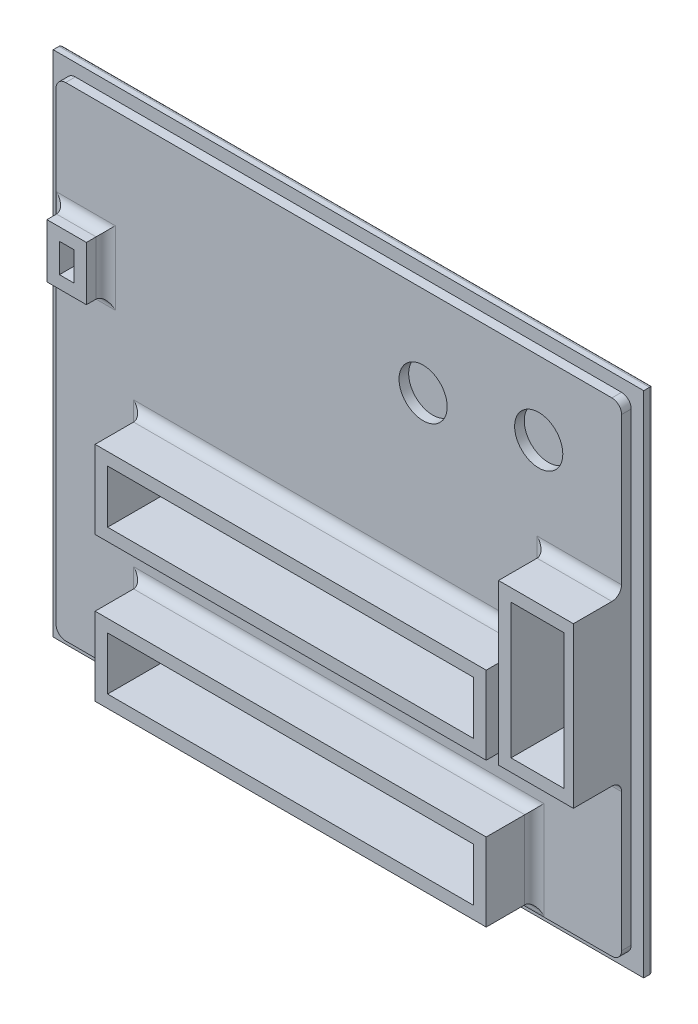
SolidWorks part; units mm, degrees
ref_plane "Płaszczyzna przednia" through (0, 0, 0) normal (0, 0, 1) x (1, 0, 0)
ref_plane "Płaszczyzna górna" through (0, 0, 0) normal (0, 1, 0) x (1, 0, 0)
ref_plane "Płaszczyzna prawa" through (0, 0, 0) normal (1, 0, 0) x (0, 0, -1)
sketch "Outside dim" plane through (0, 0, 0) normal (0, 0, 1) x (1, 0, 0)
  line L1 (-30.65, 26.4) -> (30.65, 26.4)
  line L2 (-30.65, 26.4) -> (-30.65, -26.4)
  line L3 (-30.65, -26.4) -> (30.65, -26.4)
  line L4 (30.65, 26.4) -> (30.65, -26.4)
  point P4 (0, 26.4)
  point P6 (-30.65, 0)
  dimension "D1" = 61.3
  dimension "D2" = 52.8
sketch "Inside dim" plane through (0, 0, 0) normal (0, 0, 1) x (1, 0, 0)
  line L1 (-29.35, 25.1) -> (29.35, 25.1)
  line L2 (-29.35, 25.1) -> (-29.35, -25.1)
  line L3 (-29.35, -25.1) -> (29.35, -25.1)
  line L4 (29.35, 25.1) -> (29.35, -25.1)
  point P4 (0, 25.1)
  point P6 (-29.35, 0)
  dimension "D1" = 58.7
  dimension "D2" = 50.2
extrude "Dodanie-wyciągnięcie1" add sketch "Outside dim" against normal blind 1
extrude "Dodanie-wyciągnięcie2" add sketch "Inside dim" along normal blind 1
sketch "PCB dim" plane through (0, 0, 1) normal (0, 0, 1) x (1, 0, 0)
  line L1 (-28.75, 24.5) -> (28.75, 24.5)
  line L2 (-28.75, 24.5) -> (-28.75, -24.5)
  line L3 (-28.75, -24.5) -> (28.75, -24.5)
  line L4 (28.75, 24.5) -> (28.75, -24.5)
  point P4 (0, 24.5)
  point P6 (-28.75, 0)
  dimension "D1" = 57.5
  dimension "D2" = 49
sketch "Capacitors" plane through (0, 0, 1) normal (0, 0, 1) x (1, 0, 0)
  circle A0 centre (8.75, 15.75) radius 2.5
  circle A1 centre (20.75, 17.5) radius 2.5
  dimension "D1" = 5
  dimension "D2" = 5
  dimension "D3" = 8
  dimension "D4" = 7
  dimension "D5" = 8.75
  dimension "D6" = 20
extrude "Capacitors cutout" cut sketch "Capacitors" against normal up to surface (1 mm away) up to face at (0, 0, 0)
sketch "Reset button" plane through (0, 0, 1) normal (0, 0, 1) x (1, 0, 0)
  line L0 (-28.75, 24.5) -> (-28.75, -24.5) construction
  line L1 (-24.2, 13.8) -> (-28.3, 13.8)
  line L2 (-24.2, 13.8) -> (-24.2, 8.2)
  line L3 (-24.2, 8.2) -> (-28.3, 8.2)
  line L4 (-28.3, 13.8) -> (-28.3, 8.2)
  line L5 (-25.5, 12.5) -> (-27, 12.5)
  line L6 (-25.5, 12.5) -> (-25.5, 9.5)
  line L7 (-25.5, 9.5) -> (-27, 9.5)
  line L8 (-27, 12.5) -> (-27, 9.5)
  line L9 (-28.75, 24.5) -> (28.75, 24.5) construction
  point P8 (-26.25, 13.8)
  point P11 (-27, 11)
  dimension "D1" = 1.3
  dimension "D2" = 1.3
  dimension "D3" = 1.3
  dimension "D4" = 1.3
  dimension "D5" = 2.5
  dimension "D6" = 13.5
  dimension "D7" = 1.5
  dimension "D8" = 3
extrude "Reset button shield" add sketch "Reset button" along normal blind 2 contours L4 L3 L2 L1
extrude "Reset button cutout" cut sketch "Szkic5<3>" against normal through all both and the other way through all contours L5 L8 L7 L6
sketch "Szkic5<3>" plane through (0, 0, 1) normal (0, 0, 1) x (1, 0, 0) same geometry as "Reset button"
sketch "SWDIO" plane through (0, 0, 1) normal (0, 0, 1) x (1, 0, 0)
  line L0 (28.75, 24.5) -> (28.75, -24.5) construction
  line L1 (22.875, 6.5) -> (28.375, 6.5)
  line L2 (22.875, 6.5) -> (22.875, -7.5)
  line L3 (22.875, -7.5) -> (28.375, -7.5)
  line L4 (28.375, 6.5) -> (28.375, -7.5)
  line L5 (21.575, 7.8) -> (29.35, 7.8)
  line L6 (21.575, 7.8) -> (21.575, -8.8)
  line L7 (21.575, -8.8) -> (29.35, -8.8)
  line L8 (29.35, 7.8) -> (29.35, -8.8)
  line L9 (29.35, -25.1) -> (29.35, 25.1) construction
  point P10 (25.625, -7.5)
  point P11 (22.875, -0.5)
  dimension "D1" = 5.5
  dimension "D2" = 14
  dimension "D3" = 1.3
  dimension "D4" = 1.3
  dimension "D5" = 1.3
  dimension "D7" = 3.125
  dimension "D8" = 25
extrude "SWDIO shield" add sketch "SWDIO" along normal blind 5 contours L5 L8 L7 L6
extrude "SWDIO cutout" cut sketch "Szkic6<3>" against normal through all both and the other way through all contours L1 L4 L3 L2
sketch "Szkic6<3>" plane through (0, 0, 1) normal (0, 0, 1) x (1, 0, 0) same geometry as "SWDIO"
sketch "Art skin connectors" plane through (0, 0, 1) normal (0, 0, 1) x (1, 0, 0)
  line L0 (-28.75, -24.5) -> (28.75, -24.5) construction
  line L1 (-19, -2.2) -> (19, -2.2)
  line L2 (-19, -2.2) -> (-19, -7.7)
  line L3 (-19, -7.7) -> (19, -7.7)
  line L4 (19, -2.2) -> (19, -7.7)
  line L5 (-19, -17.2) -> (19, -17.2)
  line L6 (-19, -17.2) -> (-19, -22.7)
  line L7 (-19, -22.7) -> (19, -22.7)
  line L8 (19, -17.2) -> (19, -22.7)
  line L9 (-20.3, -15.9) -> (20.3, -15.9)
  line L10 (-20.3, -15.9) -> (-20.3, -24)
  line L11 (-20.3, -24) -> (20.3, -24)
  line L12 (20.3, -15.9) -> (20.3, -24)
  line L13 (-20.3, -0.9) -> (20.3, -0.9)
  line L14 (-20.3, -0.9) -> (-20.3, -9)
  line L15 (-20.3, -9) -> (20.3, -9)
  line L16 (20.3, -0.9) -> (20.3, -9)
  point P16 (0, -2.2)
  point P17 (0, -17.2)
  point P20 (0, -24.5)
  point P21 (-19, -19.95)
  point P23 (-19, -4.95)
  dimension "D1" = 38
  dimension "D2" = 1.3
  dimension "D3" = 1.3
  dimension "D4" = 1.3
  dimension "D5" = 1.3
  dimension "D6" = 1.3
  dimension "D7" = 1.3
  dimension "D8" = 5.5
  dimension "D9" = 5.5
  dimension "D10" = 1.3
  dimension "D11" = 1.3
  dimension "D12" = 4.55
  dimension "D13" = 19.55
extrude "Art skin connectors shield" add sketch "Art skin connectors" along normal up to surface (5 mm away) up to face at (25.625, -0.5, 6)
extrude "Art skin connectors cutout" cut sketch "Szkic7<2>" against normal through all both and the other way through all contours L8 L7 L6 L5 | L1 L4 L3 L2
sketch "Szkic7<2>" plane through (0, 0, 1) normal (0, 0, 1) x (1, 0, 0) same geometry as "Art skin connectors"
fillet "Bottom of print curve" radius 0.4 20 edges at (19, -19.95, -1) (0, -22.7, -1) (-19, -19.95, -1) (0, -17.2, -1) (19, -4.95, -1) (0, -7.7, -1) (-19, -4.95, -1) (0, -2.2, -1) (28.375, -0.5, -1) (25.625, -7.5, -1) (22.875, -0.5, -1) (25.625, 6.5, -1) (0, -26.4, -1) (30.65, 0, -1) (0, 26.4, -1) (-30.65, 0, -1) (-26.25, 9.5, -1) (-27, 11, -1) (-26.25, 12.5, -1) (-25.5, 11, -1)
fillet "Side mount surve" radius 1 4 edges at (29.35, -25.1, 0.5) (-29.35, -25.1, 0.5) (29.35, 25.1, 0.5) (-29.35, 25.1, 0.5)
fillet "Curve all shields" radius 1 15 edges at (0, -24, 1) (-28.3, 11, 1) (25.4625, 7.8, 1) (-26.25, 13.8, 1) (-24.2, 11, 1) (-26.25, 8.2, 1) (0, -0.9, 1) (-20.3, -4.95, 1) (0, -15.9, 1) (-20.3, -19.95, 1) (21.575, -0.5, 1) (20.3, -19.95, 1) (20.3, -4.95, 1) (0, -9, 1) (25.4625, -8.8, 1)
